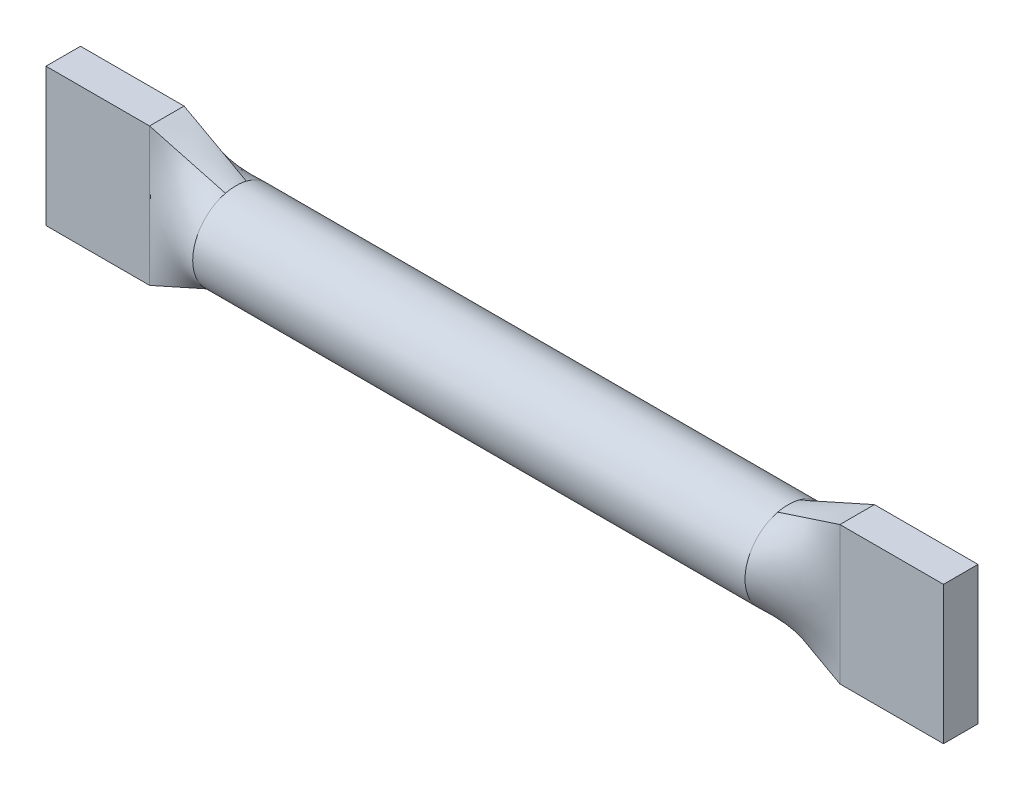
SolidWorks part; units mm, degrees
material "3.0517 (EN-AW 3003)"
ref_plane "Front Plane" through (0, 0, 0) normal (0, 0, 1) x (1, 0, 0)
ref_plane "Top Plane" through (0, 0, 0) normal (0, 1, 0) x (1, 0, 0)
ref_plane "Right Plane" through (0, 0, 0) normal (1, 0, 0) x (0, 0, -1)
sketch "Sketch1" plane through (0, 0, 0) normal (1, 0, 0) x (0, 0, -1)
  circle A0 centre (0, 0) radius 0.625
  dimension "D1" = 1.25
extrude "Boss-Extrude1" add sketch "Sketch1" along normal mid plane 8
ref_plane "Plane1" through (5, 0, 0) normal (1, 0, 0) x (0, 0, -1)
sketch "Sketch2" plane through (5, 0, 0) normal (1, 0, 0) x (0, 0, -1)
  line L1 (0.25, -1) -> (-0.25, -1)
  line L2 (0.25, -1) -> (0.25, 1)
  line L3 (0.25, 1) -> (-0.25, 1)
  line L4 (-0.25, -1) -> (-0.25, 1)
  line L5 (0.25, -1) -> (-0.25, 1) construction
  line L6 (0.25, 1) -> (-0.25, -1) construction
  point P0 (0, 0)
  dimension "D1" = 2
  dimension "D2" = 0.5
sketch "Sketch3" plane through (4, 0, 0) normal (1, 0, 0) x (0, 0, -1)
  circle A1 centre (0, 0) radius 0.625
  circle A2 centre (0, 0) radius 0.625
  dimension "D1" = 0
loft "Loft1" add profiles "Sketch2", "Sketch3" connector at (5, -1, 0.25) connector at (4, 0, -0.625)
sketch "Sketch4" plane through (5, 0, 0) normal (1, 0, 0) x (0, 0, -1)
  line L4 (-0.25, 1) -> (-0.25, -1)
  line L5 (-0.25, -1) -> (0.25, -1)
  line L6 (0.25, -1) -> (0.25, 1)
  line L7 (0.25, 1) -> (-0.25, 1)
  line L8 (-0.25, 1) -> (-0.25, -1)
  line L9 (-0.25, -1) -> (0.25, -1)
  line L10 (0.25, -1) -> (0.25, 1)
  line L11 (0.25, 1) -> (-0.25, 1)
  dimension "D1" = 0
extrude "Boss-Extrude2" add sketch "Sketch4" along normal blind 1.5
mirror "Mirror1" about plane through (0, 0, 0) normal (1, 0, 0) of "Boss-Extrude2", "Loft1"
